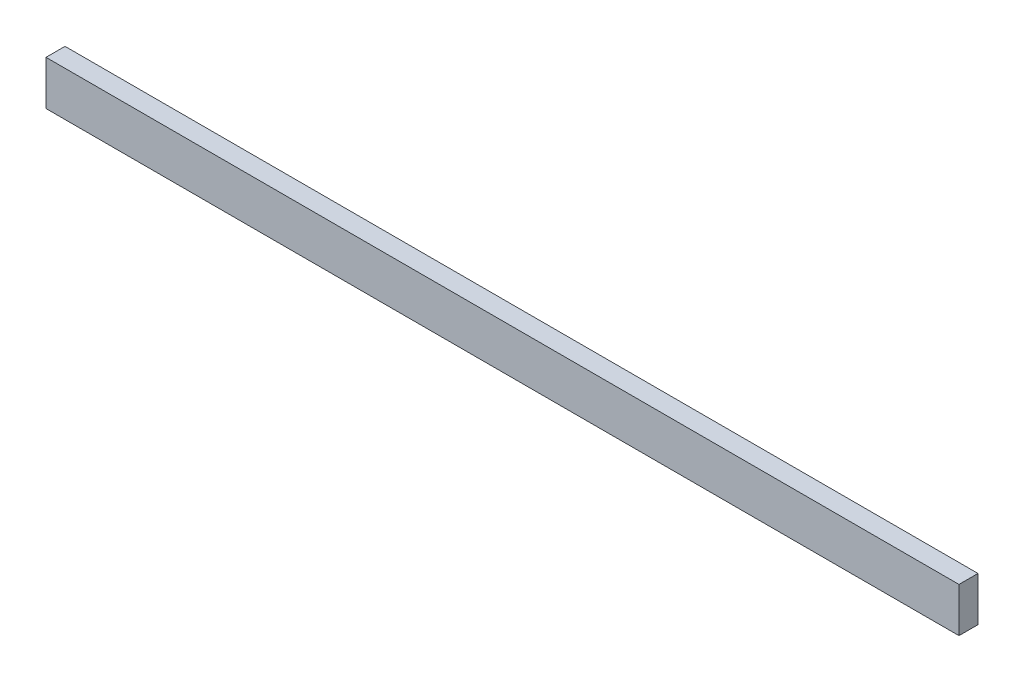
SolidWorks part; units mm, degrees
material "Pine"
ref_plane "Front Plane" through (0, 0, 0) normal (0, 0, 1) x (1, 0, 0)
ref_plane "Top Plane" through (0, 0, 0) normal (0, 1, 0) x (1, 0, 0)
ref_plane "Right Plane" through (0, 0, 0) normal (1, 0, 0) x (0, 0, -1)
sketch "Sketch1" plane through (0, 0, 0) normal (0, 0, 1) x (1, 0, 0)
  line L1 (0, 0) -> (1828.8, 0)
  line L2 (0, 0) -> (0, 88.9)
  line L3 (0, 88.9) -> (1828.8, 88.9)
  line L4 (1828.8, 0) -> (1828.8, 88.9)
  dimension "D1" = 1828.8
  dimension "D2" = 88.9
extrude "Boss-Extrude1" add sketch "Sketch1" along normal blind 38.1
